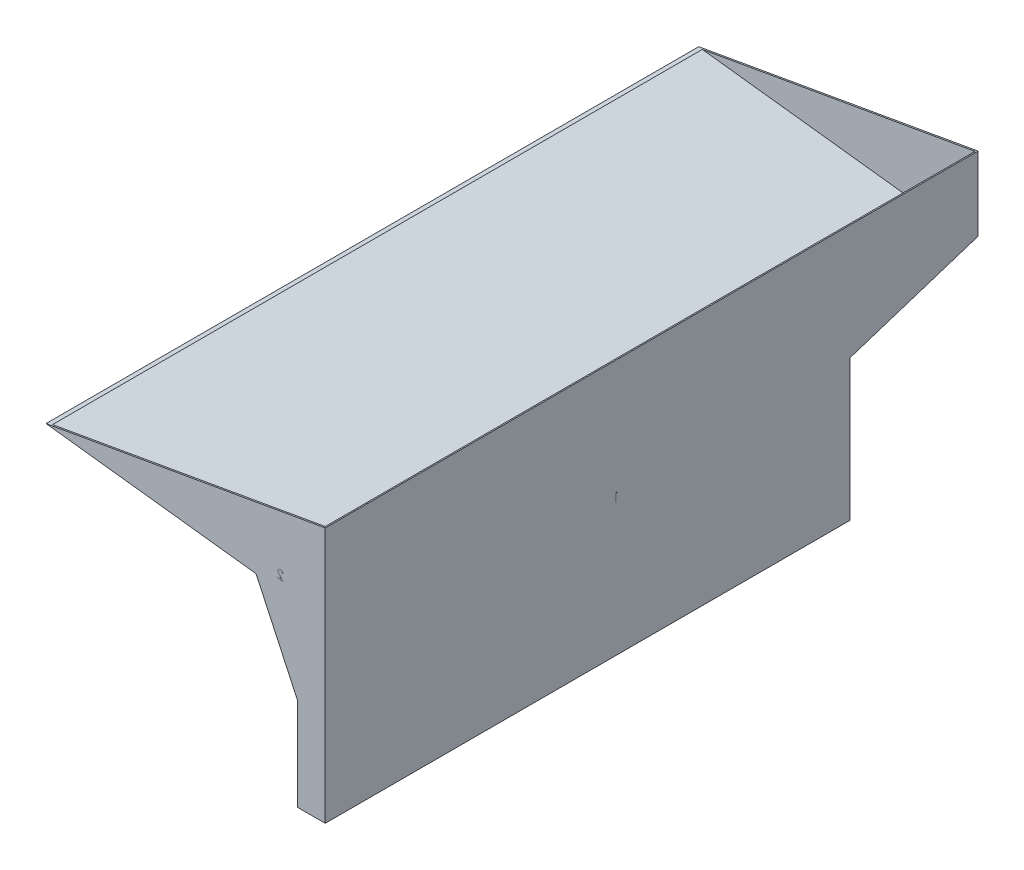
SolidWorks part; units mm, degrees
material "Melamine"
ref_plane "Front Plane" through (0, 0, 0) normal (0, 0, 1) x (1, 0, 0)
ref_plane "Top Plane" through (0, 0, 0) normal (0, 1, 0) x (1, 0, 0)
ref_plane "Right Plane" through (0, 0, 0) normal (1, 0, 0) x (0, 0, -1)
other "Center of Mass"
sketch "Sketch2" plane through (0, 0, 0) normal (0, 0, 1) x (1, 0, 0)
  line L0 (0, 0) -> (-88.7498, 190.3246)
  line L1 (-88.7498, 190.3246) -> (-540.3388, 244.1441)
  line L2 (-540.3388, 244.1441) -> (60, 350)
  line L3 (60, 350) -> (60, -200)
  line L4 (60, -200) -> (0, -200)
  line L5 (0, -200) -> (0, 0)
  dimension "D1" = 155
  dimension "D2" = 609.6
  dimension "D3" = 550
  dimension "D4" = 200
  dimension "D5" = 60
  dimension "D6" = 210
  dimension "D7" = 280
extrude "Boss-Extrude1" add sketch "Sketch2" along normal mid plane 1403.35
shell "Shell1" thickness 3.175 removed face at (-240.1694, 297.072, 0)
sketch "Sketch3" plane through (0, 0, 701.675) normal (0, 0, 1) x (1, 0, 0)
  line L1 (9, -187.3) -> (51, -187.3)
  line L2 (9, -187.3) -> (9, 102.7)
  line L3 (9, 102.7) -> (51, 102.7)
  line L4 (51, -187.3) -> (51, 102.7)
  line L6 (0, -200) -> (60, -200) construction
  point P6 (30, -200)
  point P7 (30, -187.3)
  dimension "D1" = 42
  dimension "D2" = 12.7
  dimension "D3" = 290
extrude "Cut-Extrude1" cut sketch "Sketch3" against normal blind 20
sketch "Sketch7" plane through (0, 0, 0) normal (-1, 0, 0) x (0, 0, 1)
  line L1 (701.675, -200) -> (426.675, -200)
  line L2 (701.675, -200) -> (701.675, 102.7)
  line L3 (701.675, 102.7) -> (426.675, 102.7)
  line L4 (426.675, -200) -> (426.675, 102.7)
  dimension "D1" = 275
  dimension "D2" = 302.7
extrude "Cut-Extrude5" cut sketch "Sketch7" against normal mid plane 200
sketch "Sketch9" plane through (60, 0, 0) normal (1, 0, 0) x (0, 0, -1)
  line L1 (-426.675, 102.7) -> (-701.675, 102.7)
  line L2 (-426.675, 102.7) -> (-426.675, 191.216)
  line L3 (-426.675, 191.216) -> (-701.675, 191.216)
  line L4 (-701.675, 102.7) -> (-701.675, 191.216)
  line L5 (-701.675, 191.216) -> (-426.675, 102.7)
  line M2 (-701.675, 102.7) -> (-426.675, 102.7)
  line M7 (-701.675, 350) -> (-701.675, 102.7)
  dimension "D1" = 88.516
extrude "Cut-Extrude7" cut sketch "Sketch9" against normal up to vertex (148.7498 mm away) contours L5 M7 M2 region at (60, 132.2053, 610.0083) up to point (-88.7498, 190.3246, 701.675)
sketch "Sketch11" plane through (0, -31.385, 10.1021) normal (0, -0.9519, 0.3064) x (1, 0, 0)
  line L0 (60, 726.5152) -> (60, 437.6206)
  line L1 (60, 437.6206) -> (-47.8898, 437.6206)
  line L2 (-47.8898, 437.6206) -> (-86.0836, 726.5152)
  line L3 (-86.0836, 726.5152) -> (60, 726.5152)
  line L4 (-88.7498, 726.5152) -> (60, 726.5152) construction
extrude "Boss-Extrude3" add sketch "Sketch11" against normal blind 3.175
sketch "Sketch12" plane through (3.175, 0, 0) normal (1, 0, 0) x (0, 0, -1)
  line L0 (-426.675, -196.825) -> (688.975, -79.5655)
  line L1 (688.975, -79.5655) -> (688.975, -82.7405)
  line L2 (-396.4669, -196.825) -> (-426.675, -196.825)
  line L3 (701.675, -200) -> (701.675, 350) construction
  line L4 (688.975, -82.7405) -> (-396.4669, -196.825)
  line L5 (-396.4669, -196.825) -> (-396.4669, -193.65)
  line M5 (-426.675, -196.825) -> (698.5, -196.825)
  dimension "D1" = 3.175
  dimension "D2" = 12.7
  dimension "D3" = 6
  dimension "D4" = 3.175
  dimension "D5" = 3.175
extrude "Boss-Extrude4" add sketch "Sketch12" along normal up to surface (53.65 mm away) contours L5 L4 L1 L0 | L5 L0 M5 region at (3.175, -195.7667, 406.5363) region at (3.175, -138.1952, -146.2541) up to face at (56.825, 101.026, 182.7217)
chamfer "Chamfer1" distance 6.35 angle 45 1 edges at (30, -196.825, 426.675) first distance on face at (30, -138.1952, -131.15)
sketch "Sketch14" plane through (60, 0, 0) normal (1, 0, 0) x (0, 0, -1)
  line L0 (-426.675, 102.7) -> (-426.675, -200) construction
  line L1 (-426.675, -200) -> (701.675, -200) construction
  text T0 "1" font "Century Gothic" height in points 72
  dimension "D1" = 496.5296
  dimension "D2" = 284.9328
extrude "Cut-Extrude8" cut sketch "Sketch14" against normal blind 0.1
sketch "Sketch15" plane through (0, 0, -701.675) normal (0, 0, -1) x (-1, 0, 0)
  text T0 "2" font "Century Gothic" height in points 72
extrude "Cut-Extrude9" cut sketch "Sketch15" against normal blind 0.1
sketch "Sketch16" plane through (21.1219, 177.2303, 0) normal (-0.1183, -0.993, 0) x (0.993, -0.1183, 0)
  text T0 "3" font "Century Gothic" height in points 72
extrude "Cut-Extrude10" cut sketch "Sketch16" against normal blind 0.1
sketch "Sketch17" plane through (0, 0, 0) normal (-0.9063, -0.4226, 0) x (0, 0, 1)
  text T0 "4" font "Century Gothic" height in points 72
extrude "Cut-Extrude11" cut sketch "Sketch17" against normal blind 0.1
sketch "Sketch18" plane through (0, 0, 0) normal (-1, 0, 0) x (0, 0, 1)
  text T0 "5" font "Century Gothic" height in points 72
extrude "Cut-Extrude12" cut sketch "Sketch18" against normal blind 0.1
sketch "Sketch19" plane through (0, -200, 0) normal (0, -1, 0) x (1, 0, 0)
  text T0 "6" font "Century Gothic" height in points 72
extrude "Cut-Extrude13" cut sketch "Sketch19" against normal blind 0.1
sketch "Sketch20" plane through (0, -31.385, 10.1021) normal (0, -0.9519, 0.3064) x (1, 0, 0)
  text T0 "7" font "Century Gothic" height in points 72
extrude "Cut-Extrude14" cut sketch "Sketch20" against normal blind 0.1
sketch "Sketch21" plane through (0, 0, 701.675) normal (0, 0, 1) x (1, 0, 0)
  text T0 "8" font "Century Gothic" height in points 72
extrude "Cut-Extrude15" cut sketch "Sketch21" against normal blind 0.1
mirror "Mirror1" about plane through (0, 0, -701.675) normal (0, 0, 1) of bodies 122
sketch "Sketch22" plane through (0, 0, 0) normal (-1, 0, 0) x (0, 0, 1)
  line L5 (-701.675, -200) -> (1024.7166, -200)
  line L6 (-701.675, -200) -> (-701.675, 602.0407)
  line L7 (-701.675, 602.0407) -> (1024.7166, 602.0407)
  line L8 (1024.7166, -200) -> (1024.7166, 602.0407)
extrude "Cut-Extrude16" cut sketch "Sketch22" against normal through all both and the other way through all
